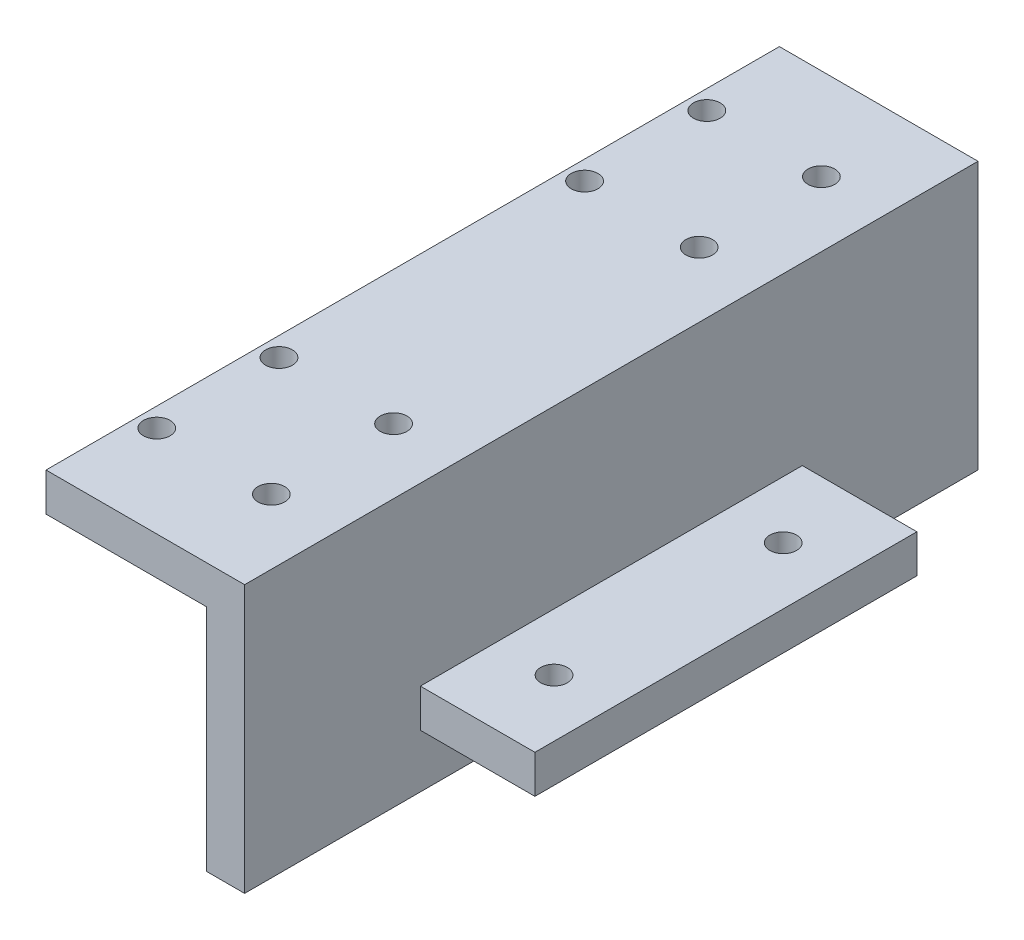
SolidWorks part; units mm, degrees
ref_plane "Front Plane" through (0, 0, 0) normal (0, 0, 1) x (1, 0, 0)
ref_plane "Top Plane" through (0, 0, 0) normal (0, 1, 0) x (1, 0, 0)
ref_plane "Right Plane" through (0, 0, 0) normal (1, 0, 0) x (0, 0, -1)
sketch "Sketch1" plane through (0, 0, 0) normal (0, 1, 0) x (1, 0, 0)
  line L0 (0, 48) -> (0, -48) construction
  line L1 (-10, 48) -> (10, 48)
  line L2 (-10, 48) -> (-10, -48)
  line L3 (-10, -48) -> (10, -48)
  line L4 (10, 48) -> (10, -48) construction
  line L5 (-10, 48) -> (10, -48) construction
  line L6 (-10, -48) -> (10, 48) construction
  line L7 (-7.5, 36) -> (7.5, 36) construction
  line L8 (-7.5, 36) -> (7.5, 20) construction
  line L9 (-10, 0) -> (10, 0) construction
  line L10 (-7.5, -36) -> (7.5, -20) construction
  line L11 (-7.5, -36) -> (7.5, -36) construction
  line L12 (-7.5, 20) -> (7.5, 20) construction
  line L13 (10, 48) -> (11, 48)
  line L14 (11, 48) -> (11, -48)
  line L15 (11, -48) -> (10, -48)
  circle A0 centre (-7.5, 36) radius 1.75
  circle A1 centre (7.5, 36) radius 1.75
  circle A2 centre (-7.5, 20) radius 1.75
  circle A3 centre (7.5, 20) radius 1.75
  circle A4 centre (7.5, -20) radius 1.75
  circle A5 centre (-7.5, -20) radius 1.75
  circle A6 centre (7.5, -36) radius 1.75
  circle A7 centre (-7.5, -36) radius 1.75
  point P0 (0, 0)
  point P16 (0, 36)
  dimension "D2" = 3.5
  dimension "D1" = 20
  dimension "D3" = 15
  dimension "D4" = 16
  dimension "D5" = 12
  dimension "D6" = 20
  dimension "D7" = 1
extrude "Boss-Extrude1" add sketch "Sketch1" along normal blind 5
sketch "Sketch2" plane through (11, 0, 0) normal (1, 0, 0) x (0, 0, -1)
  line L1 (-48, 5) -> (48, 5)
  line L2 (-48, 5) -> (-48, -30)
  line L3 (-48, -30) -> (48, -30)
  line L5 (48, 5) -> (48, -30)
  line L6 (48, 5) -> (48, 0) construction
  line L7 (-48, 5) -> (-48, 0) construction
  line L8 (-48, 5) -> (48, 5) construction
  dimension "D1" = 35
extrude "Boss-Extrude2" add sketch "Sketch2" along normal blind 5
sketch "Sketch3" plane through (16, 0, 0) normal (1, 0, 0) x (0, 0, -1)
  line L0 (0, 5) -> (0, -30) construction
  line L1 (-25, -18) -> (25, -18)
  line L2 (-25, -18) -> (-25, -23)
  line L3 (-25, -23) -> (25, -23)
  line L4 (25, -18) -> (25, -23)
  line L5 (48, 5) -> (-48, 5) construction
  line L6 (-48, -30) -> (48, -30) construction
  point P10 (0, -18)
  dimension "D1" = 5
  dimension "D2" = 50
  dimension "D3" = 7
extrude "Boss-Extrude3" add sketch "Sketch3" along normal blind 15
sketch "Sketch4" plane through (0, -18, 0) normal (0, 1, 0) x (1, 0, 0)
  line L0 (16, 0) -> (31, 0) construction
  line L1 (16, 25) -> (16, -25) construction
  line L2 (31, 25) -> (31, -25) construction
  line L3 (23.5, -15) -> (23.5, 15) construction
  circle A0 centre (23.5, 15) radius 1.75
  circle A1 centre (23.5, -15) radius 1.75
  point P8 (23.5, 0)
  dimension "D1" = 30
  dimension "D2" = 3.5
extrude "Cut-Extrude1" cut sketch "Sketch4" against normal through all
